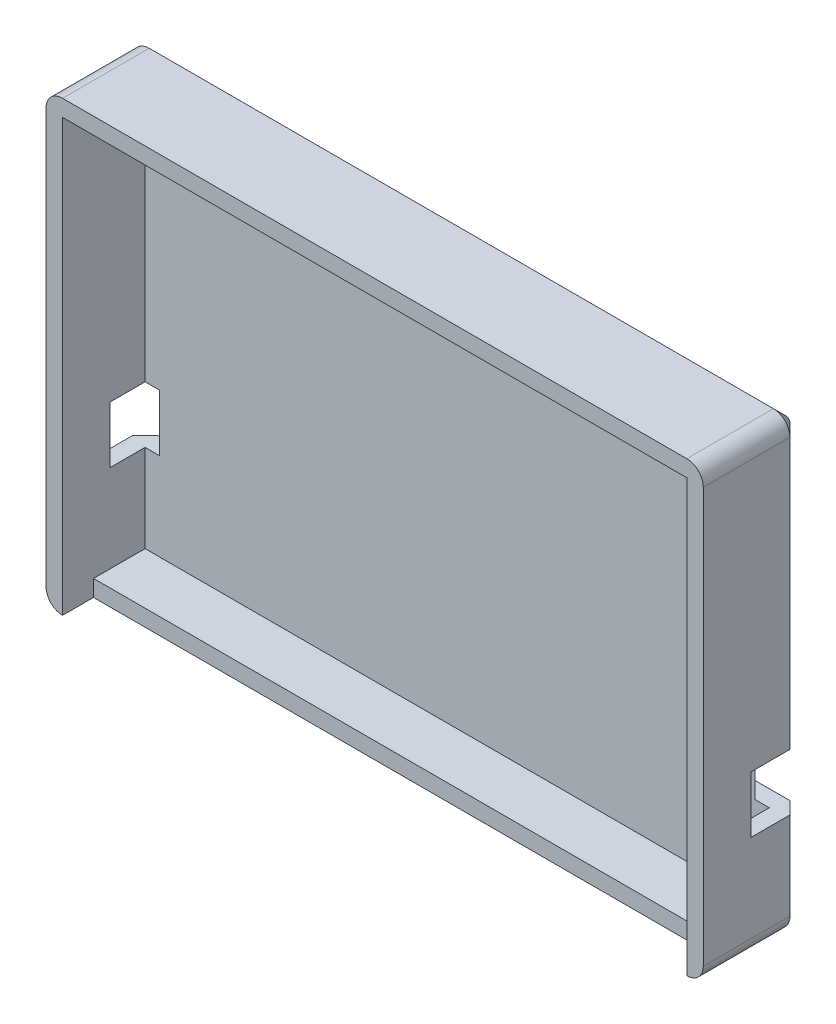
SolidWorks part; units mm, degrees
ref_plane "Front Plane" through (0, 0, 0) normal (0, 0, 1) x (1, 0, 0)
ref_plane "Top Plane" through (0, 0, 0) normal (0, 1, 0) x (1, 0, 0)
ref_plane "Right Plane" through (0, 0, 0) normal (1, 0, 0) x (0, 0, -1)
sketch "Sketch1" plane through (0, 0, 0) normal (0, 0, 1) x (1, 0, 0)
  line L0 (-30.25, -20.1) -> (-30.25, 20.1) construction
  line L1 (-29.25, -19.1) -> (29.25, -19.1) construction
  line L2 (-29.25, -19.1) -> (-29.25, 19.1) construction
  line L3 (-29.25, 19.1) -> (29.25, 19.1) construction
  line L4 (29.25, -19.1) -> (29.25, 19.1) construction
  line L5 (0, 19.1) -> (0, -19.1) construction
  line L6 (-29.25, 0) -> (29.25, 0) construction
  line L7 (-30.25, 20.1) -> (30.25, 20.1) construction
  line L8 (30.25, -20.1) -> (30.25, 20.1) construction
  line L9 (-30.25, -20.1) -> (30.25, -20.1) construction
  line L10 (-31.85, -21.7) -> (-31.85, 21.7)
  line L11 (-31.85, 21.7) -> (31.85, 21.7)
  line L12 (31.85, -21.7) -> (31.85, 21.7)
  line L13 (-31.85, -21.7) -> (31.85, -21.7)
  point P0 (0, 0)
  dimension "D1" = 58.5
  dimension "D2" = 38.2
  dimension "D3" = 1
  dimension "D4" = 1.6
extrude "Boss-Extrude1" add sketch "Sketch1" along normal blind 1.6
sketch "Sketch2" plane through (0, 0, 1.6) normal (0, 0, 1) x (1, 0, 0)
  line L1 (31.85, -21.7) -> (-31.85, -21.7)
  line L2 (31.85, -21.7) -> (31.85, 21.7)
  line L3 (31.85, 21.7) -> (-31.85, 21.7)
  line L4 (-31.85, -21.7) -> (-31.85, 21.7)
  line L5 (0, 21.7) -> (0, -21.7) construction
  line L6 (31.85, 0) -> (-31.85, 0) construction
  line L7 (30.25, -20.1) -> (-30.25, -20.1)
  line L8 (30.25, -20.1) -> (30.25, 20.1)
  line L9 (30.25, 20.1) -> (-30.25, 20.1)
  line L10 (-30.25, -20.1) -> (-30.25, 20.1)
  line L11 (0, 20.1) -> (0, -20.1) construction
  line L12 (30.25, 0) -> (-30.25, 0) construction
  point P0 (0, 0)
  point P4 (0, 0)
  point P8 (0, 0)
  point P9 (0, 0)
extrude "Boss-Extrude2" add sketch "Sketch2" along normal blind 8
sketch "Sketch4" plane through (0, -20.1, 0) normal (0, 1, 0) x (1, 0, 0)
  line L0 (-30.25, -9.6) -> (-30.25, -1.6) construction
  line L1 (-30.25, -6.6) -> (30.25, -6.6)
  line L2 (-30.25, -6.6) -> (-30.25, -9.6)
  line L3 (-30.25, -9.6) -> (30.25, -9.6)
  line L4 (30.25, -6.6) -> (30.25, -9.6)
  line L5 (-30.25, -1.6) -> (30.25, -1.6) construction
  dimension "D1" = 5
extrude "Cut-Extrude1" cut sketch "Sketch4" against normal through all
sketch "Sketch5" plane through (0, 0, 0) normal (0, 0, -1) x (-1, 0, 0)
  line L0 (29.25, -19.1) -> (-29.25, -19.1) construction
  line L1 (-31.85, -6.1) -> (-29.25, -6.1)
  line L2 (-31.85, -6.1) -> (-31.85, -11.6)
  line L3 (-31.85, -11.6) -> (-29.25, -11.6)
  line L4 (-29.25, -6.1) -> (-29.25, -11.6)
  line L5 (-30.55, -11.6) -> (-30.55, -6.1) construction
  line L6 (-31.85, -8.85) -> (-29.25, -8.85) construction
  line L7 (-31.85, -21.7) -> (-31.85, 21.7) construction
  line L9 (-29.25, -19.1) -> (-29.25, 19.1) construction
  line L10 (0, 19.1) -> (0, -19.1) construction
  line L11 (0, 19.1) -> (0, -19.1) construction
  line L12 (31.85, -8.85) -> (29.25, -8.85) construction
  line L13 (30.55, -11.6) -> (30.55, -6.1) construction
  line L14 (29.25, -6.1) -> (29.25, -11.6)
  line L15 (31.85, -11.6) -> (29.25, -11.6)
  line L16 (31.85, -6.1) -> (31.85, -11.6)
  line L17 (31.85, -6.1) -> (29.25, -6.1)
  point P0 (-30.55, -8.85)
  point P6 (0, 0)
  point P9 (0, 0)
  point P14 (0, 0)
  point P23 (30.55, -8.85)
  dimension "D1" = 5.5
  dimension "D2" = 7.5
extrude "Cut-Extrude2" cut sketch "Sketch5" against normal blind 5
chamfer "Chamfer1" distance 2 angle 45 2 edges at (-29.25, -8.85, 0) (29.25, -8.85, 0)
fillet "Fillet1" radius 1.6 4 edges at (-31.85, 21.7, 4.8) (-31.85, -21.7, 4.8) (31.85, -21.7, 4.8) (31.85, 21.7, 4.8)
chamfer "Chamfer2" distance 1.2 angle 45 10 edges at (-31.85, -15.85, 0) (31.85, -15.85, 0) (-31.3814, -21.2314, 0) (31.3814, -21.2314, 0) (0, -21.7, 0) (31.85, 7, 0) (-31.85, 7, 0) (31.3814, 21.2314, 0) (-31.3814, 21.2314, 0) (0, 21.7, 0)
